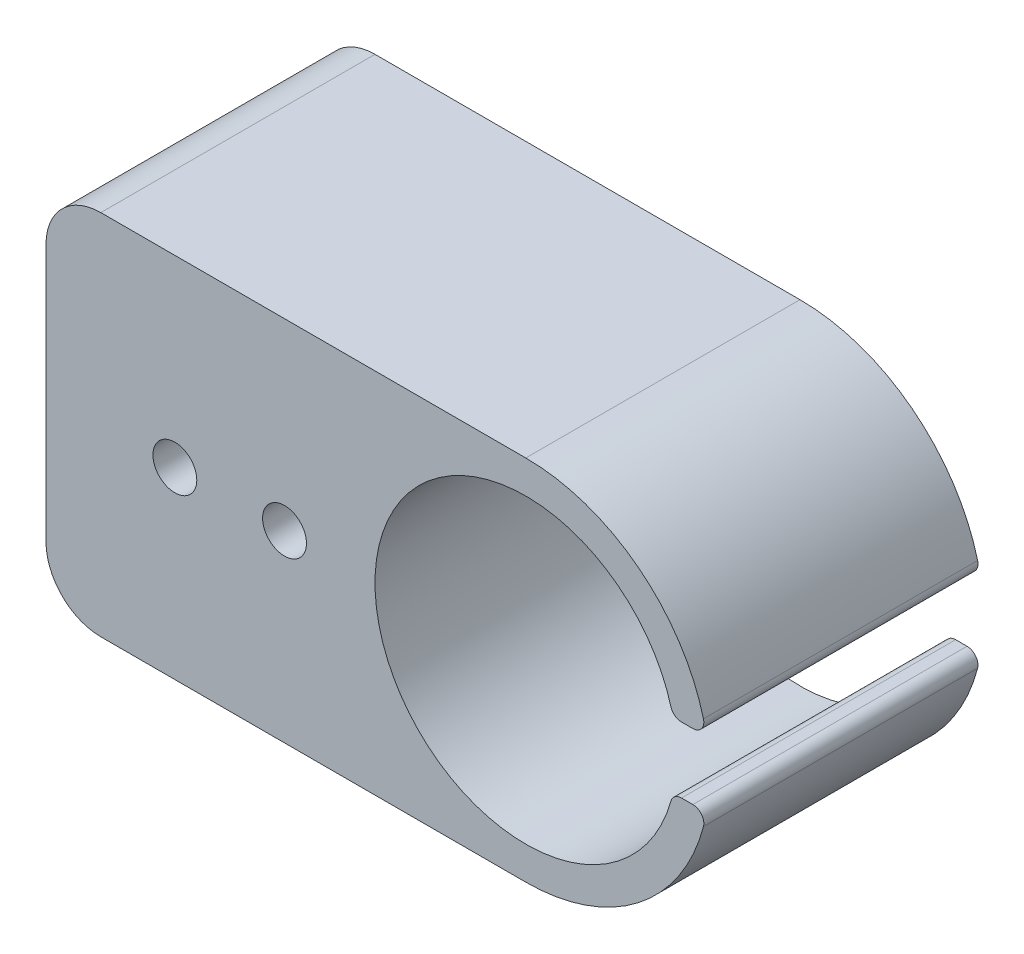
SolidWorks part; units mm, degrees
ref_plane "Plan de face" through (0, 0, 0) normal (0, 0, 1) x (1, 0, 0)
ref_plane "Plan de dessus" through (0, 0, 0) normal (0, 1, 0) x (1, 0, 0)
ref_plane "Plan de droite" through (0, 0, 0) normal (1, 0, 0) x (0, 0, -1)
sketch "Esquisse1" plane through (0, 0, 0) normal (0, 0, 1) x (1, 0, 0)
  line L0 (0, 0) -> (13.75, 0) construction
  line L1 (0, 3) -> (21.7672, 3) construction
  line L2 (0, -3) -> (21.7672, -3) construction
  line L3 (13.4187, 3) -> (16.4792, 3)
  line L4 (16.4792, -3) -> (13.4187, -3)
  line L5 (0, 0) -> (0, 16.75) construction
  line L6 (0, -16.75) -> (-43.75, -16.75)
  line L7 (-43.75, -16.75) -> (-43.75, 16.75)
  line L8 (-43.75, 16.75) -> (0, 16.75)
  circle A0 centre (0, 0) radius 13.75 construction
  arc A1 (13.4187, 3) -> (13.4187, -3) centre (0, 0) ccw
  arc A3 (16.4792, 3) -> (0, 16.75) centre (0, 0) ccw
  arc A4 (16.4792, -3) -> (0, -16.75) centre (0, 0) cw
  circle A5 centre (-32, 0) radius 2
  circle A6 centre (-22, 0) radius 2
  point P18 (-13.75, 0)
  dimension "D1" = 27.5
  dimension "D2" = 6
  dimension "D3" = 30
  dimension "D4" = 3
  dimension "D6" = 4
  dimension "D5" = 10
  dimension "D7" = 22
extrude "Boss.-Extru.1" add sketch "Esquisse1" along normal blind 25
sketch "Esquisse5" plane through (-43.75, 0, 0) normal (-1, 0, 0) x (0, 0, 1)
  line L0 (0, 0) -> (25, 0) construction
  line L2 (12.5, 0) -> (12.5, 16.75) construction
  line L3 (25, 16.75) -> (0, 16.75) construction
  line L4 (25, 16.75) -> (25, -16.75) construction
  circle A0 centre (7.5, 0) radius 2
  circle A1 centre (17.5, 0) radius 2
  dimension "D1" = 4
  dimension "D2" = 10
extrude "Enlèv. mat.-Extru.2" cut sketch "Esquisse5" against normal blind 10
fillet "Congé1" radius 5 2 edges at (-43.75, -16.75, 12.5) (-43.75, 16.75, 12.5)
fillet "Congé2" radius 1 4 edges at (16.4792, -3, 12.5) (16.4792, 3, 12.5) (13.4187, -3, 12.5) (13.4187, 3, 12.5)
